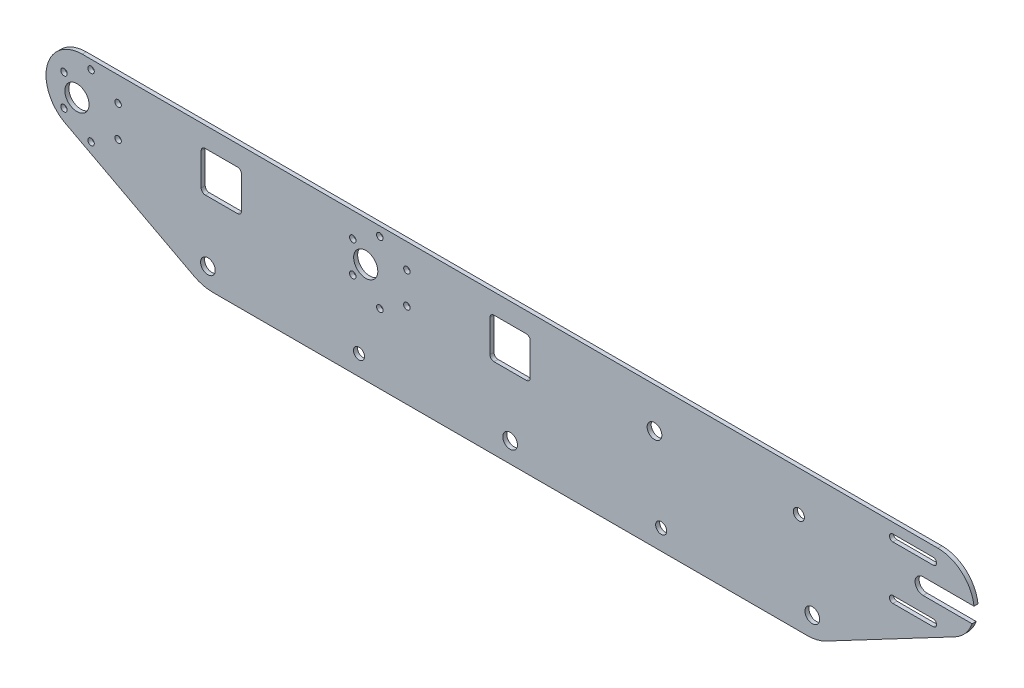
SolidWorks part; units mm, degrees
ref_plane "Plan de face" through (0, 0, 0) normal (0, 0, 1) x (1, 0, 0)
ref_plane "Plan de dessus" through (0, 0, 0) normal (0, 1, 0) x (1, 0, 0)
ref_plane "Plan de droite" through (0, 0, 0) normal (1, 0, 0) x (0, 0, -1)
sketch "Esquisse1" plane through (0, 0, 0) normal (0, 0, 1) x (1, 0, 0)
  line L0 (0, 0) -> (0, 122.747) construction
  line L1 (-215, -20) -> (215, -20) construction
  line L2 (-215, -20) -> (-215, 20) construction
  line L3 (-215, 20) -> (215, 20) construction
  line L4 (215, -20) -> (215, 20) construction
  line L5 (-215, -20) -> (215, 20) construction
  line L6 (-215, 20) -> (215, -20) construction
  line L7 (-1220, 0) -> (-150, 0) construction
  line L8 (-284.959, 40) -> (-247.3, 40)
  line L9 (248.3333, 40) -> (284.959, 40)
  line L10 (150, 0) -> (150, -20) construction
  line L11 (150, -20) -> (-150, -20) construction
  line L12 (-150, 0) -> (-150, -20) construction
  line L13 (150, 0) -> (-150, -20) construction
  line L14 (150, -20) -> (-150, 0) construction
  line L15 (-284.959, 40) -> (-247.3, 20.1016)
  line L16 (-152.4795, -30) -> (152.4795, -30)
  line L17 (284.959, 40) -> (248.3333, 20.6476)
  line L18 (-215, 20) -> (-71.6667, 20) construction
  line L19 (-71.6667, 20) -> (71.6667, 20) construction
  line L20 (71.6667, 20) -> (215, 20) construction
  line L21 (150, 0) -> (193.5165, 0) construction
  line L27 (-247.3, 20.1016) -> (-152.4795, -30)
  line L28 (248.3333, 20.6476) -> (152.4795, -30)
  line L29 (-247.3, 40) -> (248.3333, 40)
  circle A0 centre (-215, 20) radius 6
  circle A1 centre (-150, -20) radius 3.65
  circle A2 centre (150, -20) radius 3.65
  circle A3 centre (215, 20) radius 3.65
  circle A4 centre (0, -20) radius 3.65
  circle A5 centre (-71.6667, 20) radius 6
  circle A6 centre (71.6667, 20) radius 3.65
  point P0 (0, 0)
  point P8 (0, -10)
  point P21 (0, -30)
  dimension "D8" = 7.3
  dimension "D11" = 12
  dimension "D1" = 430
  dimension "D2" = 40
  dimension "D3" = 300
  dimension "D4" = 20
  dimension "D5" = 15
  dimension "D6" = 10
  dimension "D7" = 10
extrude "Boss.-Extru.1" add sketch "Esquisse1" along normal blind 2
fillet "Congé1" radius 18 2 edges at (-284.959, 40, 1) (284.959, 40, 1)
fillet "Congé2" radius 20 2 edges at (-152.4795, -30, 1) (152.4795, -30, 1)
hole_wizard "Dégagement M32" positions "Esquisse6" profile "Esquisse5" hole size "M3" standard "Ansi Metric" end condition through all
sketch "Esquisse6" plane through (0, 0, 0) normal (0, 0, -1) x (-1, 0, 0)
  line L0 (-200, 33.2288) -> (-200, 6.7712)
  circle A0 centre (-215, 20) radius 20
  circle A1 centre (-215, 20) radius 7.5
  point P0 (-200, 33.2288)
  point P2 (-200, 6.7712)
  dimension "D1" = 40
  dimension "D2" = 15
  dimension "D3" = 15
sketch "Esquisse5" plane through (200, 33.2288, 0) normal (1, 0, 0) x (0, 1, 0)
  line L0 (0, 0) -> (0, 2)
  line L1 (0, 2) -> (1.7, 2)
  line L2 (1.7, 2) -> (1.7, 0)
  line L5 (1.7, 0) -> (0, 0)
  line L11 (0, -6.35) -> (0, 107.95) construction
  dimension "Diamètre du perçage jusqu'au prochain" = 3.4
  dimension "Profondeur du perçage jusqu'au prochain" = 2
sketch "Esquisse4" plane through (0, 0, 0) normal (0, 0, -1) x (-1, 0, 0)
  line L0 (-215, 24) -> (-246.6987, 24)
  line L1 (-215, 24) -> (-205, 24)
  line L2 (-215, 16) -> (-239.4934, 16)
  line L3 (-215, 16) -> (-205, 16)
  line L4 (-215, 24) -> (-215, 16)
  line L8 (-147.5205, -30) -> (147.5205, -30)
  line L9 (156.8641, -27.6833) -> (220.7728, 6.0851)
  line L10 (156.8641, -27.6833) -> (220.7728, 6.0851)
  line L11 (212.3636, 40) -> (-212.3636, 40)
  line L12 (212.3636, 40) -> (-212.3636, 40)
  line L13 (-220.7728, 6.0851) -> (-156.8641, -27.6833)
  line L14 (-220.7728, 6.0851) -> (-156.8641, -27.6833)
  line L16 (-147.5205, -30) -> (147.5205, -30)
  arc A2 (-205, 24) -> (-205, 16) centre (-205, 20) cw
  circle A3 centre (-215, 20) radius 3.65 construction
  arc A6 (147.5205, -30) -> (156.8641, -27.6833) centre (147.5205, -10) ccw
  arc A7 (147.5205, -30) -> (156.8641, -27.6833) centre (147.5205, -10) ccw
  arc A8 (-156.8641, -27.6833) -> (-147.5205, -30) centre (-147.5205, -10) ccw
  arc A9 (-156.8641, -27.6833) -> (-147.5205, -30) centre (-147.5205, -10) ccw
  arc A12 (220.7728, 6.0851) -> (212.3636, 40) centre (212.3636, 22) ccw
  arc A13 (220.7728, 6.0851) -> (212.3636, 40) centre (212.3636, 22) ccw
  arc A14 (-212.3636, 40) -> (-220.7728, 6.0851) centre (-212.3636, 22) ccw
  arc A15 (-212.3636, 40) -> (-220.7728, 6.0851) centre (-212.3636, 22) ccw
  point P12 (-215, 20)
  circle M25 centre (-215, 20) radius 3.65
  arc M41 (-212.3636, 40) -> (-220.7728, 6.0851) centre (-212.3636, 22) ccw
  dimension "D2" = 10
  dimension "D3" = 8
  dimension "D1" = 0
extrude "Enlèv. mat.-Extru.1" cut sketch "Esquisse4" against normal through all contours A2 L1 L3 M25 | L2 L0 M25 M41 region at (223.8109, 20.0485, 0) region at (207.1433, 20, 0)
sketch "Esquisse7" plane through (0, 0, 0) normal (0, 0, -1) x (-1, 0, 0)
  line L0 (-200, 34.9288) -> (-210, 34.9288)
  line L1 (-200, 8.4712) -> (-210, 8.4712)
  line L2 (-210, 31.5288) -> (-200, 31.5288)
  line L3 (-200, 31.5288) -> (-190, 31.5288)
  line L4 (-210, 5.0712) -> (-200, 5.0712)
  line L5 (-190, 34.9288) -> (-200, 34.9288)
  line L6 (-200, 31.5288) -> (-200, 34.9288)
  line L7 (-200, 5.0712) -> (-190, 5.0712)
  line L8 (-190, 8.4712) -> (-200, 8.4712)
  line L9 (-200, 5.0712) -> (-200, 8.4712)
  circle A0 centre (-200, 33.2288) radius 1.7 construction
  arc A1 (-190, 34.9288) -> (-190, 31.5288) centre (-190, 33.2288) cw
  arc A2 (-210, 34.9288) -> (-210, 31.5288) centre (-210, 33.2288) ccw
  arc A3 (-190, 8.4712) -> (-190, 5.0712) centre (-190, 6.7712) cw
  arc A4 (-210, 8.4712) -> (-210, 5.0712) centre (-210, 6.7712) ccw
  circle A5 centre (-200, 6.7712) radius 1.7 construction
  point P11 (-200, 33.2288)
  point P19 (-200, 6.7712)
  circle M8 centre (-200, 33.2288) radius 1.7
  circle M9 centre (-200, 6.7712) radius 1.7
  dimension "D1" = 10
extrude "Enlèv. mat.-Extru.2" cut sketch "Esquisse7" against normal through all contours L1 A4 L4 M9 | A3 L8 L7 M9 | A1 L5 L3 M8 | L0 A2 L2 M8 region at (206.3352, 33.2288, 0) region at (193.6648, 33.2288, 0) region at (206.3352, 6.7712, 0) region at (193.6648, 6.7712, 0)
sketch "Esquisse8" plane through (0, 0, 0) normal (0, 0, -1) x (-1, 0, 0)
  line L0 (199.334, 20) -> (153.1405, 20) construction
  line L1 (51.2433, 27.75) -> (51.2433, 12.25) construction
  line L2 (194.5766, 27.75) -> (194.5766, 12.25) construction
  line L3 (194.5766, 12.25) -> (208, 4.5) construction
  line L4 (208, 4.5) -> (221.4234, 12.25) construction
  line L5 (221.4234, 12.25) -> (221.4234, 27.75) construction
  line L6 (221.4234, 27.75) -> (208, 35.5) construction
  line L7 (208, 35.5) -> (194.5766, 27.75) construction
  line L8 (51.2433, 12.25) -> (64.6667, 4.5) construction
  line L9 (64.6667, 4.5) -> (78.0901, 12.25) construction
  line L10 (78.0901, 12.25) -> (78.0901, 27.75) construction
  line L11 (-220.7728, 6.0851) -> (-156.8641, -27.6833)
  line L12 (-220.7728, 6.0851) -> (-156.8641, -27.6833)
  line L13 (-147.5205, -30) -> (147.5205, -30)
  line L14 (156.8641, -27.6833) -> (220.7728, 6.0851)
  line L15 (156.8641, -27.6833) -> (220.7728, 6.0851)
  line L16 (212.3636, 40) -> (-212.3636, 40)
  line L17 (212.3636, 40) -> (-212.3636, 40)
  line L23 (-147.5205, -30) -> (147.5205, -30)
  line L25 (-205, 16) -> (-229.3341, 16)
  line L26 (-205, 16) -> (-229.3341, 16)
  line L27 (-230.2521, 24) -> (-205, 24)
  line L28 (-230.2521, 24) -> (-205, 24)
  line L31 (78.0901, 27.75) -> (64.6667, 35.5) construction
  line L32 (64.6667, 35.5) -> (51.2433, 27.75) construction
  circle A0 centre (71.6667, 20) radius 6 construction
  circle A2 centre (215, 20) radius 6 construction
  circle A3 centre (215, 20) radius 6 construction
  circle A4 centre (208, 20) radius 15.5 construction
  circle A5 centre (208, 20) radius 13.4234 construction
  circle A6 centre (208, 35.5) radius 1.6
  circle A7 centre (194.5766, 27.75) radius 1.6
  circle A8 centre (194.5766, 12.25) radius 1.6
  circle A9 centre (208, 4.5) radius 1.6
  circle A10 centre (221.4234, 12.25) radius 1.6
  arc A12 (-156.8641, -27.6833) -> (-147.5205, -30) centre (-147.5205, -10) ccw
  arc A13 (-156.8641, -27.6833) -> (-147.5205, -30) centre (-147.5205, -10) ccw
  arc A14 (147.5205, -30) -> (156.8641, -27.6833) centre (147.5205, -10) ccw
  arc A15 (147.5205, -30) -> (156.8641, -27.6833) centre (147.5205, -10) ccw
  arc A20 (-229.3341, 16) -> (-220.7728, 6.0851) centre (-212.3636, 22) ccw
  arc A21 (-229.3341, 16) -> (-220.7728, 6.0851) centre (-212.3636, 22) ccw
  arc A22 (220.7728, 6.0851) -> (212.3636, 40) centre (212.3636, 22) ccw
  arc A23 (220.7728, 6.0851) -> (212.3636, 40) centre (212.3636, 22) ccw
  arc A24 (-212.3636, 40) -> (-230.2521, 24) centre (-212.3636, 22) ccw
  arc A25 (-212.3636, 40) -> (-230.2521, 24) centre (-212.3636, 22) ccw
  arc A26 (-205, 16) -> (-205, 24) centre (-205, 20) ccw
  arc A27 (-205, 16) -> (-205, 24) centre (-205, 20) ccw
  circle A31 centre (221.4234, 27.75) radius 1.6
  circle A32 centre (71.6667, 20) radius 6 construction
  circle A33 centre (64.6667, 20) radius 15.5 construction
  circle A34 centre (64.6667, 20) radius 13.4234 construction
  circle A35 centre (64.6667, 35.5) radius 1.6
  circle A36 centre (51.2433, 27.75) radius 1.6
  circle A37 centre (51.2433, 12.25) radius 1.6
  circle A38 centre (64.6667, 4.5) radius 1.6
  circle A39 centre (78.0901, 12.25) radius 1.6
  circle A41 centre (78.0901, 27.75) radius 1.6
  dimension "D2" = 31
  dimension "D4" = 3.2
  dimension "D5" = 31
  dimension "D7" = 3.2
  dimension "D3" = 7
  dimension "D6" = 7
  dimension "D1" = 0
extrude "Enlèv. mat.-Extru.3" cut sketch "Esquisse8" against normal through all contours A31 | A6 | A7 | A8 | A9 | A10 | A41 | A35 | A36 | A37 | A38 | A39 region at (-208, 35.5, 0) region at (-194.5766, 27.75, 0) region at (-194.5766, 12.25, 0) region at (-208, 4.5, 0) region at (-221.4234, 12.25, 0) region at (-221.4234, 27.75, 0) region at (-64.6667, 35.5, 0) region at (-51.2433, 27.75, 0) region at (-51.2433, 12.25, 0) region at (-64.6667, 4.5, 0) region at (-78.0901, 12.25, 0) region at (-78.0901, 27.75, 0)
hole_wizard "Dégagement M51" positions "Esquisse10" profile "Esquisse9" hole size "M5" standard "Ansi Metric" end condition through all
sketch "Esquisse10" plane through (0, 0, 0) normal (0, 0, -1) x (-1, 0, 0)
  line L0 (215, 20) -> (143.3333, 20) construction
  line L2 (143.3333, 20) -> (-208.7016, 20) construction
  line L3 (215, 20) -> (143.3333, 20)
  line L5 (143.3333, 20) -> (71.6667, 20)
  line L6 (71.6667, 20) -> (0, 20)
  line L7 (0, 20) -> (-71.6667, 20)
  line L8 (-71.6667, 20) -> (-143.3333, 20)
  circle A1 centre (215, 20) radius 6
  circle A2 centre (215, 20) radius 6 construction
  circle A3 centre (-71.6667, 20) radius 3.65 construction
  point P0 (143.3333, 20)
  point P2 (0, 20)
  point P4 (-143.3333, 20)
sketch "Esquisse9" plane through (-143.3333, 20, 0) normal (1, 0, 0) x (0, 1, 0)
  line L0 (0, 0) -> (0, 2)
  line L1 (0, 2) -> (2.75, 2)
  line L2 (2.75, 2) -> (2.75, 0)
  line L5 (2.75, 0) -> (0, 0)
  line L11 (0, -6.35) -> (0, 107.95) construction
  dimension "Diamètre du perçage jusqu'au prochain" = 5.5
  dimension "Profondeur du perçage jusqu'au prochain" = 2
hole_wizard "Dégagement M52" positions "Esquisse12" profile "Esquisse11" hole size "M5" standard "Ansi Metric" end condition through all
sketch "Esquisse12" plane through (0, 0, 2) normal (0, 0, 1) x (1, 0, 0)
  line L0 (-150, -20) -> (0, -20)
  line L1 (0, -20) -> (150, -20)
  circle A0 centre (-150, -20) radius 3
  circle A1 centre (0, -20) radius 3
  circle A2 centre (150, -20) radius 3
  point P17 (-75, -20)
  point P20 (75, -20)
sketch "Esquisse11" plane through (-75, -20, 2) normal (1, 0, 0) x (0, -1, 0)
  line L0 (0, 0) -> (0, 2)
  line L1 (0, 2) -> (2.75, 2)
  line L2 (2.75, 2) -> (2.75, 0)
  line L5 (2.75, 0) -> (0, 0)
  line L11 (0, -6.35) -> (0, 107.95) construction
  dimension "Diamètre du perçage jusqu'au prochain" = 5.5
  dimension "Profondeur du perçage jusqu'au prochain" = 2
sketch "Esquisse13" plane through (0, 0, 2) normal (0, 0, 1) x (1, 0, 0)
  line L1 (-153.3333, 30) -> (-133.3333, 30)
  line L2 (-153.3333, 30) -> (-153.3333, 10)
  line L3 (-153.3333, 10) -> (-133.3333, 10)
  line L4 (-133.3333, 30) -> (-133.3333, 10)
  line L5 (-153.3333, 30) -> (-133.3333, 10) construction
  line L6 (-153.3333, 10) -> (-133.3333, 30) construction
  line L7 (-10, 30) -> (10, 30)
  line L8 (-10, 30) -> (-10, 10)
  line L9 (-10, 10) -> (10, 10)
  line L10 (10, 30) -> (10, 10)
  line L11 (-10, 30) -> (10, 10) construction
  line L12 (-10, 10) -> (10, 30) construction
  point P0 (-143.3333, 20)
  point P6 (0, 20)
  dimension "D1" = 20
extrude "Enlèv. mat.-Extru.4" cut sketch "Esquisse13" against normal through all
fillet "Congé3" radius 2 8 edges at (10, 30, 1) (-10, 30, 1) (-10, 10, 1) (10, 10, 1) (-133.3333, 10, 1) (-153.3333, 10, 1) (-133.3333, 30, 1) (-153.3333, 30, 1)
